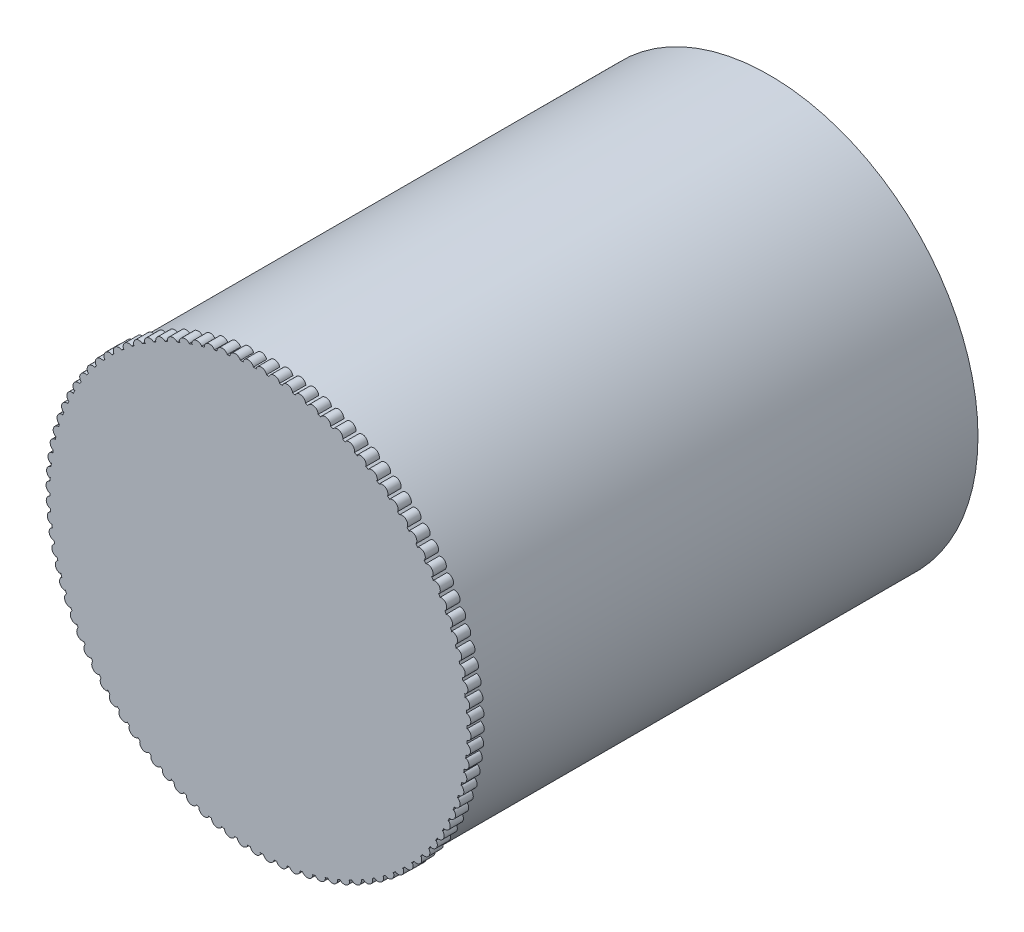
SolidWorks part; units mm, degrees
ref_plane "Front Plane" through (0, 0, 0) normal (0, 0, 1) x (1, 0, 0)
ref_plane "Top Plane" through (0, 0, 0) normal (0, 1, 0) x (1, 0, 0)
ref_plane "Right Plane" through (0, 0, 0) normal (1, 0, 0) x (0, 0, -1)
sketch "Sketch1" plane through (0, 0, 0) normal (0, 0, 1) x (1, 0, 0)
  circle A0 centre (0, 0) radius 20
  dimension "D1" = 40
extrude "Boss-Extrude1" add sketch "Sketch1" along normal blind 48.9966 contours A0
sketch "Sketch2" plane through (0, 0, 48.9966) normal (0, 0, 1) x (1, 0, 0)
  arc A1 (-1.3075, 19.9205) -> (-0.6625, 19.9423) centre (-0.9814, 19.8271) cw
  circle A3 centre (0, 0) radius 20 construction
  arc A4 (-0.0541, 19.9633) -> (0.591, 19.9446) centre (0.2655, 19.8496) cw
  arc A5 (1.1995, 19.9273) -> (1.8422, 19.8681) centre (1.5113, 19.7938) cw
  arc A6 (2.4484, 19.8126) -> (3.0861, 19.7132) centre (2.7512, 19.6598) cw
  arc A7 (3.6876, 19.6198) -> (4.3178, 19.4806) centre (3.9802, 19.4483) cw
  arc A8 (4.9123, 19.3495) -> (5.5325, 19.171) centre (5.1935, 19.16) cw
  arc A9 (6.1176, 19.0029) -> (6.7253, 18.7858) centre (6.3863, 18.7961) cw
  arc A10 (7.2987, 18.5813) -> (7.8916, 18.3264) centre (7.5539, 18.358) cw
  arc A11 (8.451, 18.0863) -> (9.0268, 17.7947) centre (8.6917, 17.8474) cw
  arc A12 (9.57, 17.52) -> (10.1263, 17.1928) centre (9.7952, 17.2665) cw
  arc A13 (10.6512, 16.8845) -> (11.1859, 16.5231) centre (10.8601, 16.6173) cw
  arc A14 (11.6904, 16.1824) -> (12.2013, 15.7881) centre (11.8821, 15.9026) cw
  arc A15 (12.6834, 15.4164) -> (13.1686, 14.9908) centre (12.8571, 15.1252) cw
  arc A16 (13.6264, 14.5896) -> (14.0839, 14.1344) centre (13.7815, 14.288) cw
  arc A17 (14.5156, 13.7052) -> (14.9436, 13.2222) centre (14.6515, 13.3945) cw
  arc A18 (15.3475, 12.7667) -> (15.7443, 12.2577) centre (15.4636, 12.4481) cw
  arc A19 (16.1189, 11.7779) -> (16.4829, 11.245) centre (16.2147, 11.4525) cw
  arc A20 (16.8266, 10.7425) -> (17.1565, 10.1878) centre (16.9018, 10.4118) cw
  arc A21 (17.4679, 9.6648) -> (17.7623, 9.0904) centre (17.5222, 9.33) cw
  arc A22 (18.0403, 8.5489) -> (18.298, 7.9572) centre (18.0735, 8.2114) cw
  arc A23 (18.5415, 7.3993) -> (18.7616, 6.7926) centre (18.5534, 7.0603) cw
  arc A24 (18.9695, 6.2204) -> (19.1511, 5.6011) centre (18.9601, 5.8814) cw
  arc A25 (19.3227, 5.017) -> (19.465, 4.3875) centre (19.292, 4.6793) cw
  arc A26 (19.5995, 3.7939) -> (19.7021, 3.1567) centre (19.5478, 3.4587) cw
  arc A27 (19.7991, 2.5557) -> (19.8614, 1.9133) centre (19.7264, 2.2245) cw
  arc A28 (19.9205, 1.3075) -> (19.9423, 0.6625) centre (19.8271, 0.9814) cw
  arc A29 (19.9633, 0.0541) -> (19.9446, -0.591) centre (19.8496, -0.2655) cw
  arc A30 (19.9273, -1.1995) -> (19.8681, -1.8422) centre (19.7938, -1.5113) cw
  arc A31 (19.8126, -2.4484) -> (19.7132, -3.0861) centre (19.6598, -2.7512) cw
  arc A32 (19.6198, -3.6876) -> (19.4806, -4.3178) centre (19.4483, -3.9802) cw
  arc A33 (19.3495, -4.9123) -> (19.171, -5.5325) centre (19.16, -5.1935) cw
  arc A34 (19.0029, -6.1176) -> (18.7858, -6.7253) centre (18.7961, -6.3863) cw
  arc A35 (18.5813, -7.2987) -> (18.3264, -7.8916) centre (18.358, -7.5539) cw
  arc A36 (18.0863, -8.451) -> (17.7947, -9.0268) centre (17.8474, -8.6917) cw
  arc A37 (17.52, -9.57) -> (17.1928, -10.1263) centre (17.2665, -9.7952) cw
  arc A38 (16.8845, -10.6512) -> (16.5231, -11.1859) centre (16.6173, -10.8601) cw
  arc A39 (16.1824, -11.6904) -> (15.7881, -12.2013) centre (15.9026, -11.8821) cw
  arc A40 (15.4164, -12.6834) -> (14.9908, -13.1686) centre (15.1252, -12.8571) cw
  arc A41 (14.5896, -13.6264) -> (14.1344, -14.0839) centre (14.288, -13.7815) cw
  arc A42 (13.7052, -14.5156) -> (13.2222, -14.9436) centre (13.3945, -14.6515) cw
  arc A43 (12.7667, -15.3475) -> (12.2577, -15.7443) centre (12.4481, -15.4636) cw
  arc A44 (11.7779, -16.1189) -> (11.245, -16.4829) centre (11.4525, -16.2147) cw
  arc A45 (10.7425, -16.8266) -> (10.1878, -17.1565) centre (10.4118, -16.9018) cw
  arc A46 (9.6648, -17.4679) -> (9.0904, -17.7623) centre (9.33, -17.5222) cw
  arc A47 (8.5489, -18.0403) -> (7.9572, -18.298) centre (8.2114, -18.0735) cw
  arc A48 (7.3993, -18.5415) -> (6.7926, -18.7616) centre (7.0603, -18.5534) cw
  arc A49 (6.2204, -18.9695) -> (5.6011, -19.1511) centre (5.8814, -18.9601) cw
  arc A50 (5.017, -19.3227) -> (4.3875, -19.465) centre (4.6793, -19.292) cw
  arc A51 (3.7939, -19.5995) -> (3.1567, -19.7021) centre (3.4587, -19.5478) cw
  arc A52 (2.5557, -19.7991) -> (1.9133, -19.8614) centre (2.2245, -19.7264) cw
  arc A53 (1.3075, -19.9205) -> (0.6625, -19.9423) centre (0.9814, -19.8271) cw
  arc A54 (0.0541, -19.9633) -> (-0.591, -19.9446) centre (-0.2655, -19.8496) cw
  arc A55 (-1.1995, -19.9273) -> (-1.8422, -19.8681) centre (-1.5113, -19.7938) cw
  arc A56 (-2.4484, -19.8126) -> (-3.0861, -19.7132) centre (-2.7512, -19.6598) cw
  arc A57 (-3.6876, -19.6198) -> (-4.3178, -19.4806) centre (-3.9802, -19.4483) cw
  arc A58 (-4.9123, -19.3495) -> (-5.5325, -19.171) centre (-5.1935, -19.16) cw
  arc A59 (-6.1176, -19.0029) -> (-6.7253, -18.7858) centre (-6.3863, -18.7961) cw
  arc A60 (-7.2987, -18.5813) -> (-7.8916, -18.3264) centre (-7.5539, -18.358) cw
  arc A61 (-8.451, -18.0863) -> (-9.0268, -17.7947) centre (-8.6917, -17.8474) cw
  arc A62 (-9.57, -17.52) -> (-10.1263, -17.1928) centre (-9.7952, -17.2665) cw
  arc A63 (-10.6512, -16.8845) -> (-11.1859, -16.5231) centre (-10.8601, -16.6173) cw
  arc A64 (-11.6904, -16.1824) -> (-12.2013, -15.7881) centre (-11.8821, -15.9026) cw
  arc A65 (-12.6834, -15.4164) -> (-13.1686, -14.9908) centre (-12.8571, -15.1252) cw
  arc A66 (-13.6264, -14.5896) -> (-14.0839, -14.1344) centre (-13.7815, -14.288) cw
  arc A67 (-14.5156, -13.7052) -> (-14.9436, -13.2222) centre (-14.6515, -13.3945) cw
  arc A68 (-15.3475, -12.7667) -> (-15.7443, -12.2577) centre (-15.4636, -12.4481) cw
  arc A69 (-16.1189, -11.7779) -> (-16.4829, -11.245) centre (-16.2147, -11.4525) cw
  arc A70 (-16.8266, -10.7425) -> (-17.1565, -10.1878) centre (-16.9018, -10.4118) cw
  arc A71 (-17.4679, -9.6648) -> (-17.7623, -9.0904) centre (-17.5222, -9.33) cw
  arc A72 (-18.0403, -8.5489) -> (-18.298, -7.9572) centre (-18.0735, -8.2114) cw
  arc A73 (-18.5415, -7.3993) -> (-18.7616, -6.7926) centre (-18.5534, -7.0603) cw
  arc A74 (-18.9695, -6.2204) -> (-19.1511, -5.6011) centre (-18.9601, -5.8814) cw
  arc A75 (-19.3227, -5.017) -> (-19.465, -4.3875) centre (-19.292, -4.6793) cw
  arc A76 (-19.5995, -3.7939) -> (-19.7021, -3.1567) centre (-19.5478, -3.4587) cw
  arc A77 (-19.7991, -2.5557) -> (-19.8614, -1.9133) centre (-19.7264, -2.2245) cw
  arc A78 (-19.9205, -1.3075) -> (-19.9423, -0.6625) centre (-19.8271, -0.9814) cw
  arc A79 (-19.9633, -0.0541) -> (-19.9446, 0.591) centre (-19.8496, 0.2655) cw
  arc A80 (-19.9273, 1.1995) -> (-19.8681, 1.8422) centre (-19.7938, 1.5113) cw
  arc A81 (-19.8126, 2.4484) -> (-19.7132, 3.0861) centre (-19.6598, 2.7512) cw
  arc A82 (-19.6198, 3.6876) -> (-19.4806, 4.3178) centre (-19.4483, 3.9802) cw
  arc A83 (-19.3495, 4.9123) -> (-19.171, 5.5325) centre (-19.16, 5.1935) cw
  arc A84 (-19.0029, 6.1176) -> (-18.7858, 6.7253) centre (-18.7961, 6.3863) cw
  arc A85 (-18.5813, 7.2987) -> (-18.3264, 7.8916) centre (-18.358, 7.5539) cw
  arc A86 (-18.0863, 8.451) -> (-17.7947, 9.0268) centre (-17.8474, 8.6917) cw
  arc A87 (-17.52, 9.57) -> (-17.1928, 10.1263) centre (-17.2665, 9.7952) cw
  arc A88 (-16.8845, 10.6512) -> (-16.5231, 11.1859) centre (-16.6173, 10.8601) cw
  arc A89 (-16.1824, 11.6904) -> (-15.7881, 12.2013) centre (-15.9026, 11.8821) cw
  arc A90 (-15.4164, 12.6834) -> (-14.9908, 13.1686) centre (-15.1252, 12.8571) cw
  arc A91 (-14.5896, 13.6264) -> (-14.1344, 14.0839) centre (-14.288, 13.7815) cw
  arc A92 (-13.7052, 14.5156) -> (-13.2222, 14.9436) centre (-13.3945, 14.6515) cw
  arc A93 (-12.7667, 15.3475) -> (-12.2577, 15.7443) centre (-12.4481, 15.4636) cw
  arc A94 (-11.7779, 16.1189) -> (-11.245, 16.4829) centre (-11.4525, 16.2147) cw
  arc A95 (-10.7425, 16.8266) -> (-10.1878, 17.1565) centre (-10.4118, 16.9018) cw
  arc A96 (-9.6648, 17.4679) -> (-9.0904, 17.7623) centre (-9.33, 17.5222) cw
  arc A97 (-8.5489, 18.0403) -> (-7.9572, 18.298) centre (-8.2114, 18.0735) cw
  arc A98 (-7.3993, 18.5415) -> (-6.7926, 18.7616) centre (-7.0603, 18.5534) cw
  arc A99 (-6.2204, 18.9695) -> (-5.6011, 19.1511) centre (-5.8814, 18.9601) cw
  arc A100 (-5.017, 19.3227) -> (-4.3875, 19.465) centre (-4.6793, 19.292) cw
  arc A101 (-3.7939, 19.5995) -> (-3.1567, 19.7021) centre (-3.4587, 19.5478) cw
  arc A102 (-2.5557, 19.7991) -> (-1.9133, 19.8614) centre (-2.2245, 19.7264) cw
  point P305 (0, 0)
  dimension "D1" = 0.3392
  dimension "D2" = 0.6625
  dimension "D3" = 0.9814
  dimension "D4" = 1.3075
  dimension "D5" = 19.8271
  dimension "D6" = 100
  dimension "D7" = 0.0541
  dimension "D8" = 0.2655
extrude "Extrude-Thin2" add sketch "Sketch2" against normal blind 1.27 from surface thin starting at face at (20, 0, 48.9966) thin type mid plane wall 0.381
